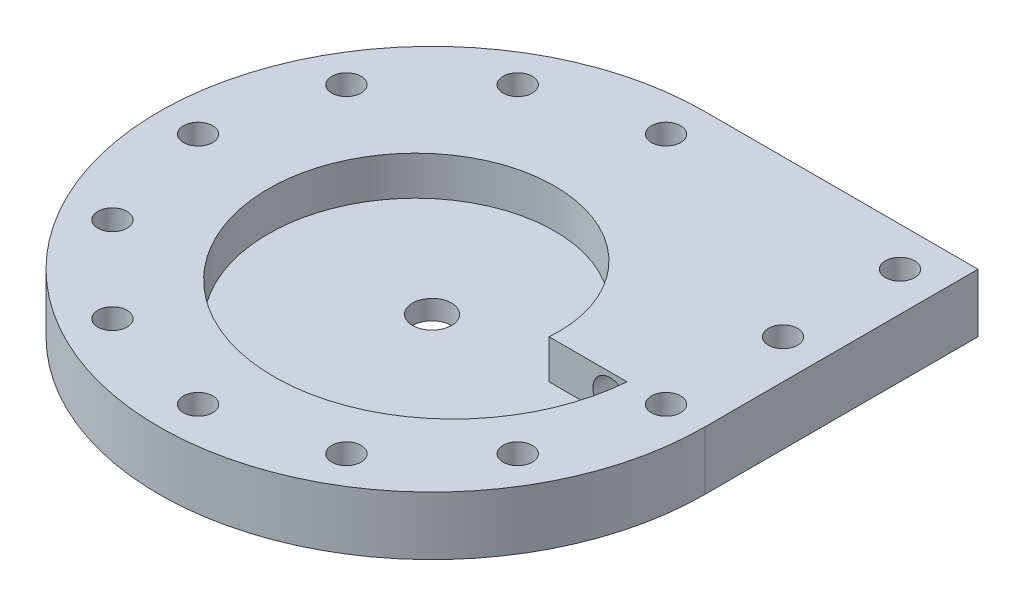
SolidWorks part; units mm, degrees
material "AISI 316 Annealed Stainless Steel Bar (SS)"
ref_plane "Front Plane" through (0, 0, 0) normal (0, 0, 1) x (1, 0, 0)
ref_plane "Top Plane" through (0, 0, 0) normal (0, 1, 0) x (1, 0, 0)
ref_plane "Right Plane" through (0, 0, 0) normal (1, 0, 0) x (0, 0, -1)
sketch "Sketch1" plane through (0, 0, 0) normal (0, 1, 0) x (1, 0, 0)
  line L0 (0, 0) -> (38.1, 0) construction
  line L1 (38.1, 0) -> (63.5, 0)
  line L2 (88.9, 0) -> (88.9, 88.9)
  line L3 (88.9, 88.9) -> (12.7, 88.9)
  line L4 (12.7, 88.9) -> (12.7, 87.9882)
  line L5 (50.8, 0) -> (50.8, 88.9) construction
  line L6 (12.7, 88.9) -> (0, 88.9)
  circle A0 centre (0, 0) radius 88.9
  circle A1 centre (0, 0) radius 6.35
  spline S0 degree 4 poles (29.2885, -21.2794) (29.769, -20.7198) (30.9322, -19.2883) (32.637, -16.8745) (34.6058, -13.3369) (36.0685, -9.7705) (36.9096, -6.9692) (37.3601, -5.0239) (37.5541, -4.0447) (37.6513, -3.509) (37.7267, -3.0616) (37.7836, -2.7031) (37.837, -2.3443) (37.887, -1.9846) (37.9337, -1.6235) (37.9713, -1.3103) (38.0012, -1.0434) (38.0252, -0.8145) (38.0441, -0.6247) (38.0671, -0.3817) (38.0915, -0.1076) (38.1092, 0.1096) (38.1353, 0.4657) (38.158, 0.8126) (38.1804, 1.2152) (38.2016, 1.695) (38.2191, 2.266) (38.2277, 2.9117) (38.2256, 3.5607) (38.2125, 4.2081) (38.1826, 5.0178) (38.1249, 5.988) (38.0261, 7.1179) (37.8701, 8.4046) (37.6714, 9.6854) (37.4302, 10.9589) (37.147, 12.2238) (36.4973, 14.7334) (35.3398, 18.111) (33.4043, 22.231) (30.3818, 26.8533) (27.0057, 30.8053) (23.1581, 34.2995) (18.9044, 37.2855) (14.3144, 39.7224) (9.4607, 41.5788) (4.418, 42.8331) (-0.7386, 43.4728) (-5.9344, 43.495) (-11.0965, 42.9051) (-16.1542, 41.7171) (-21.0407, 39.9527) (-26.8558, 37.0627) (-33.2491, 32.5691) (-39.6236, 26.01) (-45.0939, 17.1061) (-48.7256, 6.6599) (-49.8922, -4.356) (-48.5706, -15.3499) (-44.8835, -25.7672) (-39.504, -34.7106) (-32.4712, -42.4187) (-24.08, -48.6171) (-14.6624, -53.1003) (-4.5721, -55.7341) (5.8294, -56.4552) (14.8918, -55.4165) (22.4199, -53.3755) (28.4361, -50.9462) (33.0579, -48.5841) (37.454, -45.8247) (41.5922, -42.692) (45.4432, -39.2124) (48.9802, -35.4141) (52.1794, -31.3274) (55.0199, -26.9839) (57.484, -22.4163) (59.2977, -18.2533) (60.4919, -14.893) (61.2409, -12.4112) (61.666, -10.848) (61.9803, -9.5907) (62.2686, -8.3271) (62.5309, -7.0579) (62.7375, -5.9429) (62.8983, -4.9843) (63.0214, -4.1837) (63.1132, -3.5425) (63.1986, -2.8994) (63.2772, -2.2586) (63.341, -1.6884) (63.3858, -1.2582) (63.4176, -0.9312) (63.4497, -0.5879) (63.4868, -0.166) (63.5074, 0.0845) (63.5409, 0.5279) (63.5685, 0.9198) (63.5923, 1.2876) (63.6235, 1.8282) (63.6532, 2.4458) (63.6761, 3.0551) (63.6963, 3.7903) (63.7089, 4.5246) (63.7139, 5.6267) (63.6905, 7.0959) (63.6198, 8.8089) (63.4794, 10.7633) (63.2799, 12.7125) (63.0215, 14.6547) (62.5461, 17.5551) (61.8221, 20.9084) (60.8982, 24.2133) (59.78, 27.4555) (59.0683, 29.281) (58.6946, 30.1865) (58.5033, 30.6374) knots 0 0 0 0 0 0.008012 0.02003 0.032047 0.043876 0.04979 0.051762 0.053733 0.054719 0.055705 0.05669 0.057676 0.058662 0.059648 0.060633 0.061126 0.061619 0.062112 0.062605 0.06359 0.06447 0.06535 0.06623 0.06711 0.06887 0.070629 0.072389 0.074149 0.075909 0.077668 0.081188 0.084707 0.088227 0.091746 0.095266 0.098785 0.102305 0.119902 0.13398 0.148058 0.162136 0.176214 0.190293 0.204371 0.218449 0.232527 0.246605 0.260683 0.274761 0.288839 0.302917 0.316995 0.345151 0.373307 0.401463 0.429619 0.464376 0.492532 0.520688 0.548844 0.577 0.605156 0.633312 0.661468 0.689624 0.71778 0.731858 0.745936 0.760014 0.774092 0.78817 0.802248 0.816326 0.830404 0.844482 0.85856 0.872638 0.879677 0.883196 0.886716 0.890235 0.893755 0.897274 0.900794 0.902554 0.904313 0.906073 0.907833 0.909593 0.911352 0.912232 0.912672 0.913112 0.914872 0.916202 0.916867 0.917532 0.918862 0.920192 0.922853 0.924183 0.925513 0.928173 0.930833 0.936154 0.941474 0.946795 0.952115 0.957436 0.962756 0.978718 0.989359 0.994679 1 1 1 1 1 construction
  spline S1 degree 4 poles (38.1, 0) (38.1056, 0.0687) (38.1163, 0.2065) (38.1353, 0.4657) (38.158, 0.8126) (38.1804, 1.2152) (38.2016, 1.695) (38.2191, 2.266) (38.2277, 2.9117) (38.2256, 3.5607) (38.2125, 4.2081) (38.1826, 5.0178) (38.1249, 5.988) (38.0261, 7.1179) (37.8701, 8.4046) (37.6714, 9.6854) (37.4302, 10.9589) (37.147, 12.2238) (36.4973, 14.7334) (35.3398, 18.111) (33.4043, 22.231) (30.3818, 26.8533) (27.0057, 30.8053) (23.1581, 34.2995) (18.9044, 37.2855) (14.3144, 39.7224) (9.4607, 41.5788) (4.418, 42.8331) (-0.7386, 43.4728) (-5.9344, 43.495) (-11.0965, 42.9051) (-16.1542, 41.7171) (-21.0407, 39.9527) (-26.8558, 37.0627) (-33.2491, 32.5691) (-39.6236, 26.01) (-45.0939, 17.1061) (-48.7256, 6.6599) (-49.8922, -4.356) (-48.5706, -15.3499) (-44.8835, -25.7672) (-39.504, -34.7106) (-32.4712, -42.4187) (-24.08, -48.6171) (-14.6624, -53.1003) (-4.5721, -55.7341) (5.8294, -56.4552) (14.8918, -55.4165) (22.4199, -53.3755) (28.4361, -50.9462) (33.0579, -48.5841) (37.454, -45.8247) (41.5922, -42.692) (45.4432, -39.2124) (48.9802, -35.4141) (52.1794, -31.3274) (55.0199, -26.9839) (57.484, -22.4163) (59.2977, -18.2533) (60.4919, -14.893) (61.2409, -12.4112) (61.666, -10.848) (61.9803, -9.5907) (62.2686, -8.3271) (62.5309, -7.0579) (62.7375, -5.9429) (62.8983, -4.9843) (63.0214, -4.1837) (63.1132, -3.5425) (63.1986, -2.8994) (63.2772, -2.2586) (63.341, -1.6884) (63.3858, -1.2582) (63.4176, -0.9312) (63.4497, -0.5879) (63.4743, -0.3074) (63.4888, -0.1374) (63.5, 0) knots 0.06359 0.06359 0.06359 0.06359 0.06359 0.06447 0.06535 0.06623 0.06711 0.06887 0.070629 0.072389 0.074149 0.075909 0.077668 0.081188 0.084707 0.088227 0.091746 0.095266 0.098785 0.102305 0.119902 0.13398 0.148058 0.162136 0.176214 0.190293 0.204371 0.218449 0.232527 0.246605 0.260683 0.274761 0.288839 0.302917 0.316995 0.345151 0.373307 0.401463 0.429619 0.464376 0.492532 0.520688 0.548844 0.577 0.605156 0.633312 0.661468 0.689624 0.71778 0.731858 0.745936 0.760014 0.774092 0.78817 0.802248 0.816326 0.830404 0.844482 0.85856 0.872638 0.879677 0.883196 0.886716 0.890235 0.893755 0.897274 0.900794 0.902554 0.904313 0.906073 0.907833 0.909593 0.911352 0.912232 0.912672 0.913112 0.914872 0.914872 0.914872 0.914872 0.914872
  dimension "D1" = 177.8
  dimension "D4" = 12.7
  dimension "D2" = 38.1
  dimension "D3" = 76.2
extrude "Boss-Extrude1" add sketch "Sketch1" against normal blind 19.05 contours L1 S1 | A0 S1 L1 | A0 L2 L3 L4 | A0 L4 L6 region at (1.9733, 0, 8.086) region at (69.1781, 0, -68.998) region at (-61.0838, 0, 61.0838) region at (9.5283, 0, -88.6267)
extrude "Cut-Extrude1" cut sketch "Sketch1<3>" against normal blind 12.7 contours L1 S1 region at (1.9733, 0, 8.086)
sketch "Sketch1<3>" plane through (0, 0, 0) normal (0, 1, 0) x (1, 0, 0) same geometry as "Sketch1"
sketch "Sketch2" plane through (0, 0, 0) normal (0, 0, 1) x (1, 0, 0)
  line L3 (38.1, -12.7) -> (63.5, -12.7) construction
  line L4 (63.5, -12.7) -> (63.5, 0) construction
  circle A0 centre (57.9437, -7.1437) radius 5.5563
  dimension "D1" = 11.1125
extrude "Cut-Extrude3" cut sketch "Sketch2" against normal through all
hole_wizard "3/8 (0.375) Diameter Hole1" positions "3DSketch2" profile "Sketch3" hole size "3/8" standard "ANSI Inch"
sketch3d "3DSketch2"
  line L2 (76.2, 0, 0) -> (0, 0, 0) construction
  point P0 (76.2, 0, 0)
  dimension "D1" = 76.2
sketch "Sketch3" plane through (76.2, 0, 0) normal (1, 0, 0) x (0, 0, 1)
  line L0 (0, 0) -> (0, 79.0616)
  line L1 (0, 79.0616) -> (4.7625, 76.2)
  line L2 (4.7625, 76.2) -> (4.7625, 0)
  line L5 (4.7625, 0) -> (0, 0)
  line L10 (0, 79.0616) -> (-4.7625, 76.2) construction
  line L11 (0, -6.35) -> (0, 107.95) construction
  dimension "Hole Dia." = 9.525
  dimension "Hole Depth" = 76.2
  dimension "Drill Angle" = 118
pattern_circular "CirPattern1" count 12 over 360 about axis through (0, -19.05, 0) along (0, 1, 0) skipping 1, 2 of "3/8 (0.375) Diameter Hole1"
pattern_linear "LPattern1" count 3 spacing 38.1 along (0, 0, -1) of "3/8 (0.375) Diameter Hole1"
equation "\"Volute ID\" = 3"
equation "\"Volute OD\" = 4"
equation "\"D2@Sketch1\"=\"Volute ID\"/2"
